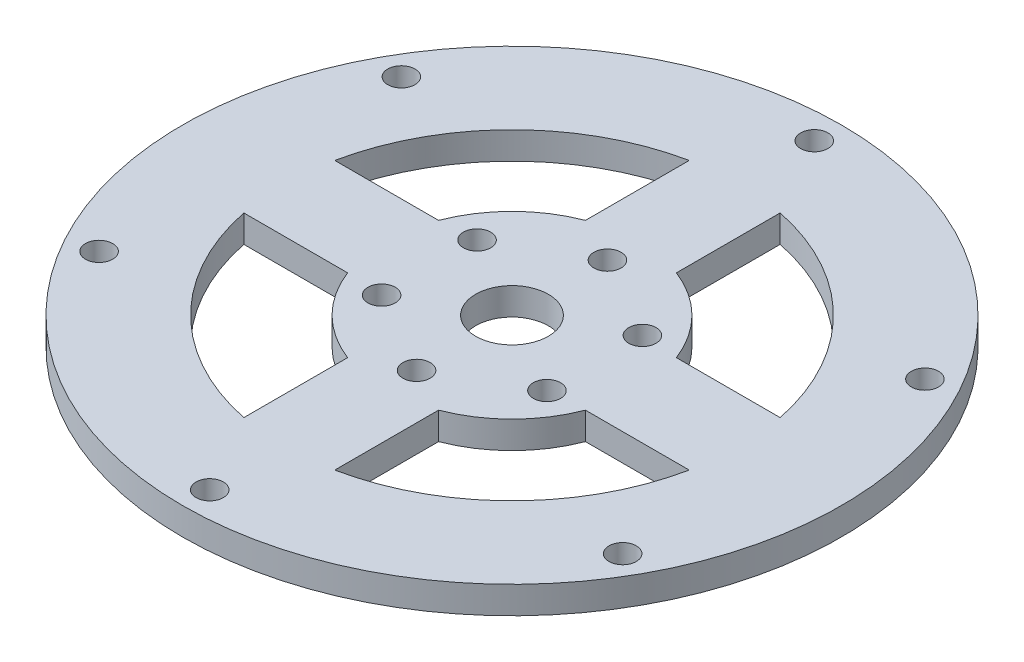
SolidWorks part; units mm, degrees
ref_plane "Front Plane" through (0, 0, 0) normal (0, 0, 1) x (1, 0, 0)
ref_plane "Top Plane" through (0, 0, 0) normal (0, 1, 0) x (1, 0, 0)
ref_plane "Right Plane" through (0, 0, 0) normal (1, 0, 0) x (0, 0, -1)
sketch "Sketch1" plane through (0, 0, 0) normal (0, 1, 0) x (1, 0, 0)
  line L0 (0, 0) -> (0, 36.25) construction
  line L9 (0, 0) -> (-36.25, 0) construction
  circle A1 centre (0, 0) radius 36.25
  point P24 (0, 0)
  dimension "D2" = 72.5
extrude "Boss-Extrude1" add sketch "Sketch1" along normal blind 3
sketch "Sketch2" plane through (0, 3, 0) normal (0, 1, 0) x (1, 0, 0)
  line L0 (0, 0) -> (0, 33.25) construction
  circle A0 centre (0, 0) radius 36.25 construction
  circle A5 centre (0, 33.25) radius 1.5
  point P0 (0, 0)
  point P1 (0, 33.3784)
  dimension "D1" = 3
  dimension "D2" = 33.25
extrude "Cut-Extrude1" cut sketch "Sketch2" against normal through all both and the other way through all
sketch "Sketch3" plane through (0, 3, 0) normal (0, 1, 0) x (1, 0, 0)
  line L0 (0, 0) -> (0, 33.25) construction
  line L1 (-5, 24.4949) -> (-5, 13.0767)
  line L2 (5, 24.4949) -> (5, 13.0767)
  line L3 (24.4949, -5) -> (13.0767, -5)
  line L4 (24.4949, 5) -> (13.0767, 5)
  line L5 (-5, -24.4949) -> (-5, -13.0767)
  line L6 (5, -24.4949) -> (5, -13.0767)
  line L7 (-24.4949, 5) -> (-13.0767, 5)
  line L8 (-24.4949, -5) -> (-13.0767, -5)
  arc A1 (-5, 13.0767) -> (-13.0767, 5) centre (0, 0) ccw
  arc A2 (-5, 24.4949) -> (-24.4949, 5) centre (0, 0) ccw
  arc A3 (-24.4949, -5) -> (-5, -24.4949) centre (0, 0) ccw
  arc A4 (24.4949, 5) -> (5, 24.4949) centre (0, 0) ccw
  arc A5 (5, -24.4949) -> (24.4949, -5) centre (0, 0) ccw
  arc A6 (-13.0767, -5) -> (-5, -13.0767) centre (0, 0) ccw
  arc A7 (5, -13.0767) -> (13.0767, -5) centre (0, 0) ccw
  arc A8 (13.0767, 5) -> (5, 13.0767) centre (0, 0) ccw
  circle A9 centre (0, 0) radius 4
  point P23 (0, 0)
  dimension "D1" = 4
  dimension "D2" = 28
  dimension "D3" = 50
  dimension "D5" = 8
  dimension "D4" = 10
extrude "Cut-Extrude2" cut sketch "Sketch3" against normal blind 8 contours A2 A1 | L2 A8 L4 A4 | L6 A7 L3 A5 | A9 | L8 A6 L5 A3 region at (-13.6588, 3, -13.6588)
pattern_circular "CirPattern1" count 6 over 360 about axis through (0, 3, 0) along (0, -1, 0) of "Cut-Extrude1"
sketch "Sketch4" plane through (0, 3, 0) normal (0, 1, 0) x (1, 0, 0)
  line L0 (0, 0) -> (0, 10.5) construction
  circle A0 centre (0, 10.5) radius 1.5
  dimension "D1" = 3
  dimension "D2" = 10.5
extrude "Cut-Extrude3" cut sketch "Sketch4" against normal through all
pattern_circular "CirPattern2" count 6 over 360 about axis through (0, 3, 0) along (0, -1, 0) of "Cut-Extrude3"
